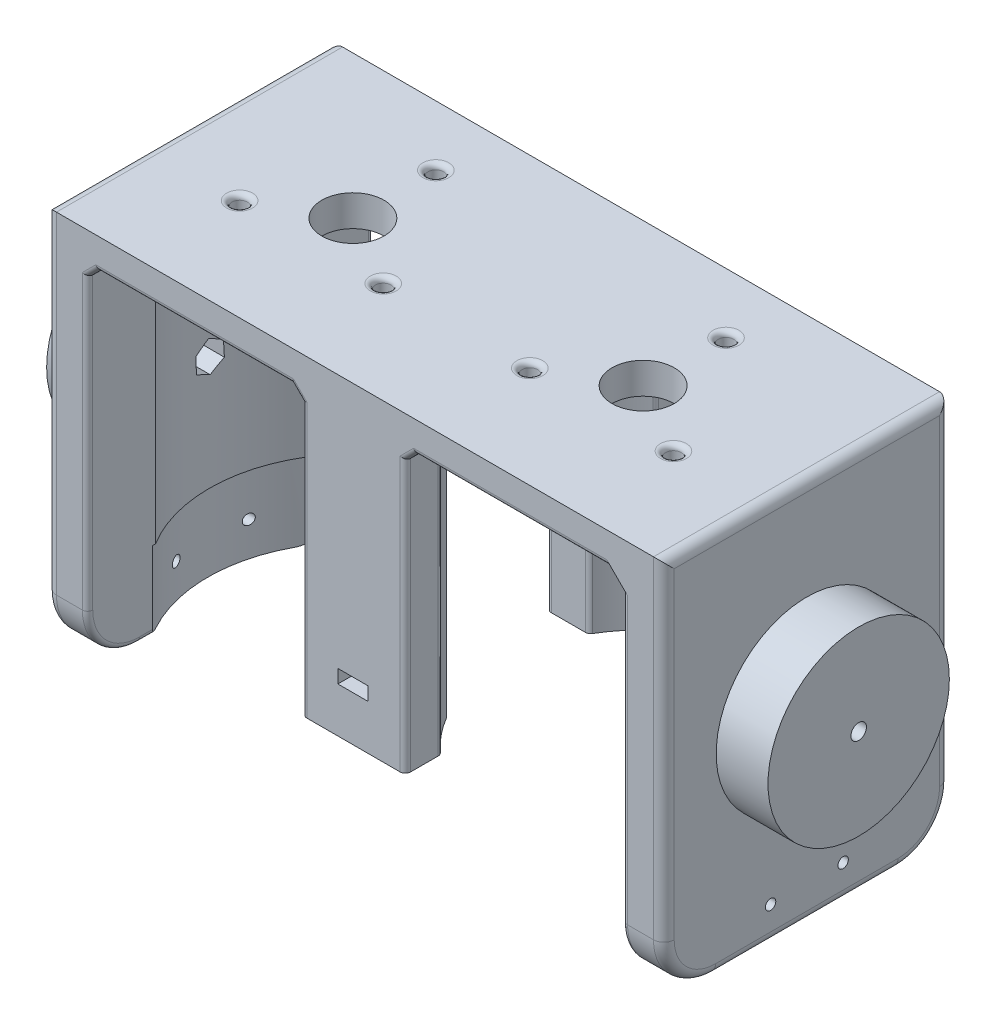
SolidWorks part; units mm, degrees
ref_plane "前视基准面" through (0, 0, 0) normal (0, 0, 1) x (1, 0, 0)
ref_plane "上视基准面" through (0, 0, 0) normal (0, 1, 0) x (1, 0, 0)
ref_plane "右视基准面" through (0, 0, 0) normal (1, 0, 0) x (0, 0, -1)
sketch "草图1" plane through (0, 0, 0) normal (0, 1, 0) x (1, 0, 0)
  line L1 (55.6, -27.6) -> (-55.6, -27.6)
  line L2 (55.6, -27.6) -> (55.6, 27.6)
  line L3 (55.6, 27.6) -> (-55.6, 27.6)
  line L4 (-55.6, -27.6) -> (-55.6, 27.6)
  line L5 (55.6, -27.6) -> (-55.6, 27.6) construction
  line L6 (55.6, 27.6) -> (-55.6, -27.6) construction
  point P0 (0, 0)
  dimension "D1" = 111.2
  dimension "D2" = 55.2
extrude "凸台-拉伸1" add sketch "草图1" along normal blind 6
sketch "草图2" plane through (0, 6, 0) normal (0, 1, 0) x (1, 0, 0)
  line L0 (0, 0) -> (28, 0) construction
  line L1 (0, 0) -> (-28, 0) construction
  line L2 (0, 27.6) -> (0, -27.6) construction
  line L3 (55.6, 27.6) -> (-55.6, 27.6) construction
  line L4 (-55.6, -27.6) -> (55.6, -27.6) construction
  circle A0 centre (28, 16) radius 1.5
  circle A1 centre (41.8564, -8) radius 1.5
  circle A2 centre (14.1436, -8) radius 1.5
  circle A3 centre (-41.8564, -8) radius 1.5
  circle A4 centre (-14.1436, -8) radius 1.5
  circle A5 centre (-28, 16) radius 1.5
  circle A6 centre (-28, 0) radius 6
  circle A7 centre (28, 0) radius 6
  point P12 (28, 0)
  dimension "D4" = 3
  dimension "D6" = 12
  dimension "D1" = 28
  dimension "D2" = 28
  dimension "D3" = 16
  dimension "D5" = 3
extrude "切除-拉伸1" cut sketch "草图2" against normal through all
sketch "草图4" plane through (0, 6, 0) normal (0, 1, 0) x (1, 0, 0)
  line L1 (55.6, 27.6) -> (59.6, 27.6)
  line L2 (55.6, 27.6) -> (55.6, -27.6)
  line L3 (55.6, -27.6) -> (59.6, -27.6)
  line L4 (59.6, 27.6) -> (59.6, -27.6)
  line L5 (-55.6, 27.6) -> (-59.6, 27.6)
  line L6 (-55.6, 27.6) -> (-55.6, -27.6)
  line L7 (-55.6, -27.6) -> (-59.6, -27.6)
  line L8 (-59.6, 27.6) -> (-59.6, -27.6)
  dimension "D1" = 4
  dimension "D2" = 4
extrude "凸台-拉伸2" add sketch "草图4" against normal blind 74
sketch "草图6" plane through (0, 0, 0) normal (0, -1, 0) x (1, 0, 0)
  line L0 (55.6, 27.6) -> (55.6, -27.6) construction
  line L1 (51.6, 27.6) -> (59.6, 27.6)
  line L2 (51.6, 27.6) -> (51.6, -27.6)
  line L3 (51.6, -27.6) -> (59.6, -27.6)
  line L4 (59.6, 27.6) -> (59.6, -27.6)
  line L5 (51.6, 27.6) -> (59.6, -27.6) construction
  line L6 (51.6, -27.6) -> (59.6, 27.6) construction
  line L7 (-55.6, 27.6) -> (-55.6, -27.6) construction
  line L8 (-51.6, 27.6) -> (-59.6, 27.6)
  line L9 (-51.6, 27.6) -> (-51.6, -27.6)
  line L10 (-51.6, -27.6) -> (-59.6, -27.6)
  line L11 (-59.6, 27.6) -> (-59.6, -27.6)
  line L12 (-51.6, 27.6) -> (-59.6, -27.6) construction
  line L13 (-51.6, -27.6) -> (-59.6, 27.6) construction
  point P0 (55.6, 0)
  point P8 (-55.6, 0)
extrude "凸台-拉伸6" add sketch "草图6" along normal up to surface (68 mm away) up to face at (-57.6, -68, 0)
sketch "草图7" plane through (0, -68, 0) normal (0, -1, 0) x (1, 0, 0)
  circle A0 centre (-28, 0) radius 27.7
  circle A1 centre (28, 0) radius 27.7
  dimension "D1" = 55.4
  dimension "D2" = 55.4
extrude "切除-拉伸2" cut sketch "草图7" against normal up to surface (68 mm away) up to face at (28, 0, 6)
fillet "圆角2" radius 10 4 edges at (55.6, -68, 27.6) (55.6, -68, -27.6) (-55.6, -68, 27.6) (-55.6, -68, -27.6)
sketch "草图8" plane through (59.6, 0, 0) normal (1, 0, 0) x (0, 0, -1)
  line L0 (0, 6) -> (0, -68) construction
  line L1 (-27.6, 6) -> (27.6, 6) construction
  line L2 (-17.6, -68) -> (17.6, -68) construction
  circle A0 centre (0, -31) radius 17.5
  dimension "D1" = 35
extrude "凸台-拉伸7" add sketch "草图8" along normal blind 10
sketch "草图9" plane through (-59.6, 0, 0) normal (-1, 0, 0) x (0, 0, 1)
  line L0 (0, 6) -> (0, -68) construction
  line L1 (-27.6, 6) -> (27.6, 6) construction
  line L2 (-17.6, -68) -> (17.6, -68) construction
  circle A0 centre (0, -31) radius 17.5
  dimension "D1" = 35
extrude "凸台-拉伸8" add sketch "草图9" along normal blind 10
sketch "草图10" plane through (-59.6, 0, 0) normal (-1, 0, 0) x (0, 0, 1)
  line L1 (2.7631, -29.5945) -> (0.1644, -27.9044)
  line L2 (0.1644, -27.9044) -> (-2.5987, -29.3098)
  line L3 (-2.5987, -29.3098) -> (-2.7631, -32.4055)
  line L4 (-2.7631, -32.4055) -> (-0.1644, -34.0956)
  line L5 (-0.1644, -34.0956) -> (2.5987, -32.6902)
  line L6 (2.5987, -32.6902) -> (2.7631, -29.5945)
  circle A0 centre (0, -31) radius 2.6847 construction
  dimension "D1" = 3.1
extrude "切除-拉伸3" cut sketch "草图10" against normal blind 10
sketch "草图11" plane through (-69.6, 0, 0) normal (-1, 0, 0) x (0, 0, 1)
  circle A0 centre (0, -31) radius 1.5
  dimension "D1" = 3
extrude "切除-拉伸4" cut sketch "草图11" against normal through all both and the other way through all
sketch "草图12" plane through (59.6, 0, 0) normal (1, 0, 0) x (0, 0, -1)
  line L1 (-2.6489, -29.2046) -> (-2.8793, -32.3963)
  line L2 (-2.8793, -32.3963) -> (-0.2304, -34.1917)
  line L3 (-0.2304, -34.1917) -> (2.6489, -32.7954)
  line L4 (2.6489, -32.7954) -> (2.8793, -29.6037)
  line L5 (2.8793, -29.6037) -> (0.2304, -27.8083)
  line L6 (0.2304, -27.8083) -> (-2.6489, -29.2046)
  circle A0 centre (0, -31) radius 2.7713 construction
  dimension "D1" = 3.2
extrude "切除-拉伸5" cut sketch "草图12" against normal blind 10
fillet "圆角5" radius 2 6 edges at (59.6, -26, 27.6) (59.6, -65.0711, 24.6711) (59.6, -68, 0) (59.6, -65.0711, -24.6711) (59.6, 6, 0) (59.6, -26, -27.6)
fillet "圆角6" radius 2 6 edges at (-59.6, -26, -27.6) (-59.6, -65.0711, -24.6711) (-59.6, -26, 27.6) (-59.6, -65.0711, 24.6711) (-59.6, 6, 0) (-59.6, -68, 0)
sketch "草图13" plane through (0, -68, 0) normal (0, -1, 0) x (1, 0, 0)
  circle A0 centre (-28, 0) radius 28
  dimension "D1" = 56
extrude "切除-拉伸6" cut sketch "草图13" against normal blind 15
mirror "镜向1" about plane through (0, 0, 0) normal (1, 0, 0) of "切除-拉伸6"
sketch "草图14" plane through (0, 0, 0) normal (0, -1, 0) x (1, 0, 0)
  line L0 (-10.2763, 27.6) -> (9.7237, 27.6)
  line L1 (-51.6, 27.6) -> (51.6, 27.6) construction
  line L2 (-10.2763, 27.6) -> (-10.2763, 21.2876)
  line L3 (9.7237, 27.6) -> (9.7237, 20.8151)
  line L4 (-3.8685, 13.6) -> (3.8685, 13.6)
  arc A0 (-3.8685, 13.6) -> (-10.2763, 21.2876) centre (-28, 0) ccw
  arc A1 (9.7237, 20.8151) -> (3.8685, 13.6) centre (28, 0) ccw
  point P10 (-0.2763, 27.6)
  dimension "D1" = 55.4
  dimension "D2" = 10
  dimension "D3" = 14
extrude "凸台-拉伸9" add sketch "草图14" along normal blind 54.4
mirror "镜向2" about plane through (0, 0, 0) normal (0, 0, 1) of "凸台-拉伸9"
sketch "草图16" plane through (0, -54.4, 0) normal (0, -1, 0) x (1, 0, 0)
  line L0 (-0.2763, 27.6) -> (-0.2763, 21.6) construction
  line L1 (9.7237, 27.6) -> (-10.2763, 27.6) construction
  line L2 (-0.2763, -27.6) -> (-0.2763, -21.6) construction
  line L3 (9.7237, -27.6) -> (-10.2763, -27.6) construction
  circle A0 centre (-0.2763, 21.6) radius 1.45
  circle A1 centre (-0.2763, -21.6) radius 1.45
  dimension "D2" = 2.9
  dimension "D4" = 2.9
  dimension "D1" = 6
  dimension "D3" = 6
extrude "切除-拉伸7" cut sketch "草图16" against normal blind 14
sketch "草图17" plane through (0, 0, 27.6) normal (0, 0, 1) x (1, 0, 0)
  line L0 (9.7237, -54.4) -> (-10.2763, -54.4) construction
  line L1 (-3.2977, -43.1) -> (2.5023, -43.1)
  line L2 (-3.2977, -43.1) -> (-3.2977, -45.7)
  line L3 (-3.2977, -45.7) -> (2.5023, -45.7)
  line L4 (2.5023, -43.1) -> (2.5023, -45.7)
  line L5 (-3.2977, -43.1) -> (2.5023, -45.7) construction
  line L6 (-3.2977, -45.7) -> (2.5023, -43.1) construction
  point P0 (-0.3977, -44.4)
  dimension "D1" = 2.6
  dimension "D2" = 5.8
  dimension "D3" = 10
extrude "切除-拉伸8" cut sketch "草图17" against normal blind 10
mirror "镜向3" about plane through (0, 0, 0) normal (0, 0, 1) of "切除-拉伸8"
sketch "草图18" plane through (59.6, 0, 0) normal (1, 0, 0) x (0, 0, -1)
  circle A0 centre (-7, -61.4) radius 1
  circle A1 centre (7, -61.4) radius 1
extrude "切除-拉伸9" cut sketch "草图18" against normal through all both and the other way through all
chamfer "倒角1" distance 2 angle 45 4 edges at (-51.6, 0, 21.0514) (-10.2763, 0, 24.4438) (51.6, 0, 21.0514) (9.7237, 0, 24.2075)
fillet "圆角7" radius 2 4 edges at (-51.6, 0, -21.0514) (-10.2763, 0, -24.4438) (51.6, 0, -21.0514) (9.7237, 0, -24.2075)
fillet "圆角8" radius 1 37 edges at (51.6, -68, -16.3339) (51.6, -65.0711, -24.6711) (51.6, -30, -27.6) (51.0142, -0.5858, -27.6) (30.6619, 0, -27.6) (10.3095, -0.5858, -27.6) (-51.6, -68, -16.3339) (-51.6, -65.0711, -24.6711) (-51.6, -30, -27.6) (-51.0142, -0.5858, -27.6) (-30.9381, 0, -27.6) (-10.8621, -0.5858, -27.6) (-10.78, -0.6729, -21.6971) (9.7237, -28.2, -27.6) (-10.2763, -28.2, -27.6) (-10.2763, -28.2, -21.2876) (9.7237, -28.2, 27.6) (-10.2763, -28.2, 27.6) (-10.2763, -28.2, 21.2876) (9.7237, -28.2, 20.8151) (3.8685, -27.2, 13.6) (-3.8685, -27.2, 13.6) (-51.6, -68, 16.3339) (-51.6, -65.0711, 24.6711) (51.6, -68, 16.3339) (51.6, -65.0711, 24.6711) (10.0082, -0.9719, -21.0614) (-50.6, -1, 27.6) (10.7237, -1, 27.6) (-11.2763, -1, 27.6) (-30.9381, 0, 27.6) (-51.6, -30, 27.6) (51.6, -30, 27.6) (30.6619, 0, 27.6) (9.7237, -28.2, -20.8151) (3.8685, -27.2, -13.6) (-3.8685, -27.2, -13.6)
fillet "圆角9" radius 1 6 edges at (-28, 6, -17.5) (-41.8564, 6, 6.5) (-14.1436, 6, 6.5) (14.1436, 6, 9.5) (28, 6, -14.5) (41.8564, 6, 9.5)
